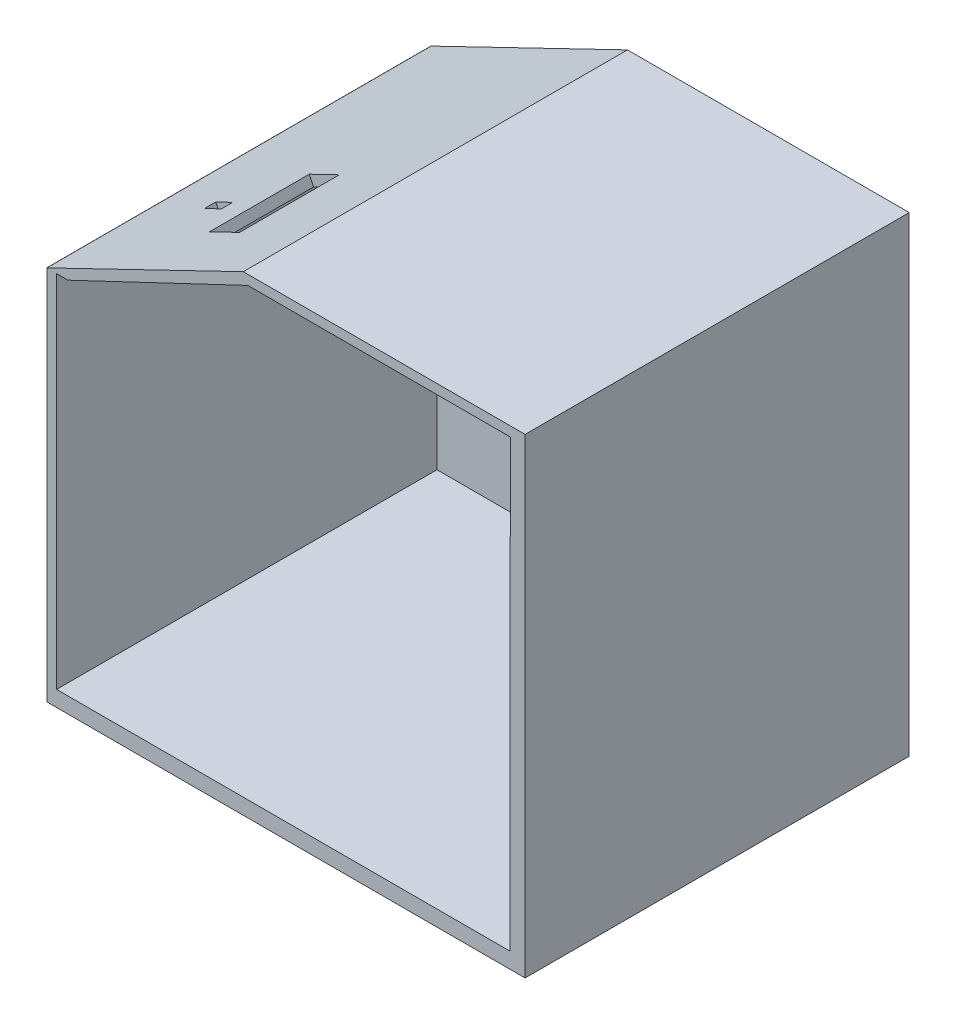
SolidWorks part; units mm, degrees
ref_plane "Front Plane" through (0, 0, 0) normal (0, 0, 1) x (1, 0, 0)
ref_plane "Top Plane" through (0, 0, 0) normal (0, 1, 0) x (1, 0, 0)
ref_plane "Right Plane" through (0, 0, 0) normal (1, 0, 0) x (0, 0, -1)
sketch "Sketch1" plane through (0, 0, 0) normal (0, 1, 0) x (1, 0, 0)
  line L5 (253.8826, 203.2185) -> (-254.1174, 203.2185)
  line L13 (249.8826, 199.2185) -> (-250.1174, 199.2185)
  line L14 (249.8826, 199.2185) -> (249.8826, -200.7815)
  line L15 (249.8826, -200.7815) -> (-250.1174, -200.7815)
  line L16 (-250.1174, 199.2185) -> (-250.1174, -200.7815)
  line L17 (249.8826, 199.2185) -> (-250.1174, -200.7815) construction
  line L18 (249.8826, -200.7815) -> (-250.1174, 199.2185) construction
  line L19 (-254.1174, 203.2185) -> (-254.1174, -204.7815)
  line L20 (253.8826, -204.7815) -> (-254.1174, -204.7815)
  line L21 (253.8826, 203.2185) -> (253.8826, -204.7815)
  point P0 (-0.1174, -0.7815)
  dimension "D1" = 4
extrude "Boss-Extrude1" add sketch "Sketch1" along normal blind 500
extrude "Boss-Extrude2" add sketch "Sketch1<3>" along normal blind 500 contours L13 L16 L15 L14 region at (-0.1174, 0, 0.7815)
sketch "Sketch1<3>" plane through (0, 0, 0) normal (0, 1, 0) x (1, 0, 0) same geometry as "Sketch1"
sketch "Sketch2" plane through (-254.1174, 0, 0) normal (-1, 0, 0) x (0, 0, 1)
  line L1 (144.7126, 324.9532) -> (24.7126, 324.9532)
  line L2 (144.7126, 324.9532) -> (144.7126, 144.9532)
  line L3 (144.7126, 144.9532) -> (24.7126, 144.9532)
  line L4 (24.7126, 324.9532) -> (24.7126, 144.9532)
extrude "Cut-Extrude1" cut sketch "Sketch2" against normal mid plane 15
sketch "Sketch4" plane through (0, 0, 204.7815) normal (0, 0, 1) x (1, 0, 0)
  line L1 (-243.6832, 399.0841) -> (238.1044, 399.0841)
  line L2 (-243.6832, 399.0841) -> (-243.6832, 16.6737)
  line L3 (-243.6832, 16.6737) -> (238.1044, 16.6737)
  line L4 (238.1044, 399.0841) -> (238.1044, 16.6737)
  point P4 (244.0961, 16.6737)
  point P5 (243.6646, 398.5145)
  point P6 (243.6741, 400.5042)
  point P7 (238.1044, 399.0841)
extrude "Cut-Extrude3" cut sketch "Sketch4" against normal mid plane 808
sketch "Sketch6" plane through (0, 0, 204.7815) normal (0, 0, 1) x (1, 0, 0)
  line L0 (-243.7005, 399.2121) -> (-256.8542, 399.2121)
  point P3 (0, 0)
sketch "Sketch8" plane through (0, 0, 204.7815) normal (0, 0, 1) x (1, 0, 0)
  line L1 (-253.9942, 399.2039) -> (-45.3295, 500.0294)
  line L2 (-45.3295, 500.0294) -> (-45.3295, 399.2039)
  line L3 (-45.3295, 399.2039) -> (-264.2758, 399.2039)
  point P5 (0, 0)
  point P7 (0, 0)
  point P8 (0, 0)
  line M8 (253.8826, 500) -> (-254.1174, 500)
  line M9 (-254.1174, 500) -> (-254.1174, 0)
extrude "Cut-Extrude4" cut sketch "Sketch8" against normal mid plane 868 contours L3 L1 M8 M9 region at (-184.5417, 466.3815, 204.7815)
sketch "Sketch9" plane through (0, 0, 204.7815) normal (0, 0, 1) x (1, 0, 0)
  line L0 (-233.5366, 398.177) -> (-40.5878, 489.7695)
  line L1 (-40.5878, 489.7695) -> (238.2024, 489.7695)
  line L2 (238.2024, 398.177) -> (238.2024, 489.7695)
  line L3 (-233.5366, 398.177) -> (243.4218, 398.177)
  point P2 (0, 0)
  point P3 (0, 0)
  point P6 (0, 0)
  point P9 (0, 0)
  line M4 (-243.6832, 399.0841) -> (238.1044, 399.0841)
  line M5 (238.1044, 399.0841) -> (238.1044, 16.6737)
extrude "Cut-Extrude5" cut sketch "Sketch9" against normal mid plane 808 contours L3 L2 L1 L0 M5 M4 region at (46.9858, 440.5697, 204.7815)
sketch "Sketch10" plane through (-204.4583, 423.1394, 0) normal (-0.4351, 0.9004, 0) x (0.9004, 0.4351, 0)
  line L1 (7.4822, -81.7554) -> (27.4822, -81.7554)
  line L2 (7.4822, -81.7554) -> (7.4822, -93.7554)
  line L3 (7.4822, -93.7554) -> (27.4822, -93.7554)
  line L4 (27.4822, -81.7554) -> (27.4822, -93.7554)
  line L5 (59.2552, -29.0227) -> (94.7552, -29.0227)
  line L6 (59.2552, -29.0227) -> (59.2552, -135.0227)
  line L7 (59.2552, -135.0227) -> (94.7552, -135.0227)
  line L8 (94.7552, -29.0227) -> (94.7552, -135.0227)
extrude "Cut-Extrude6" cut sketch "Sketch10" against normal mid plane 48
